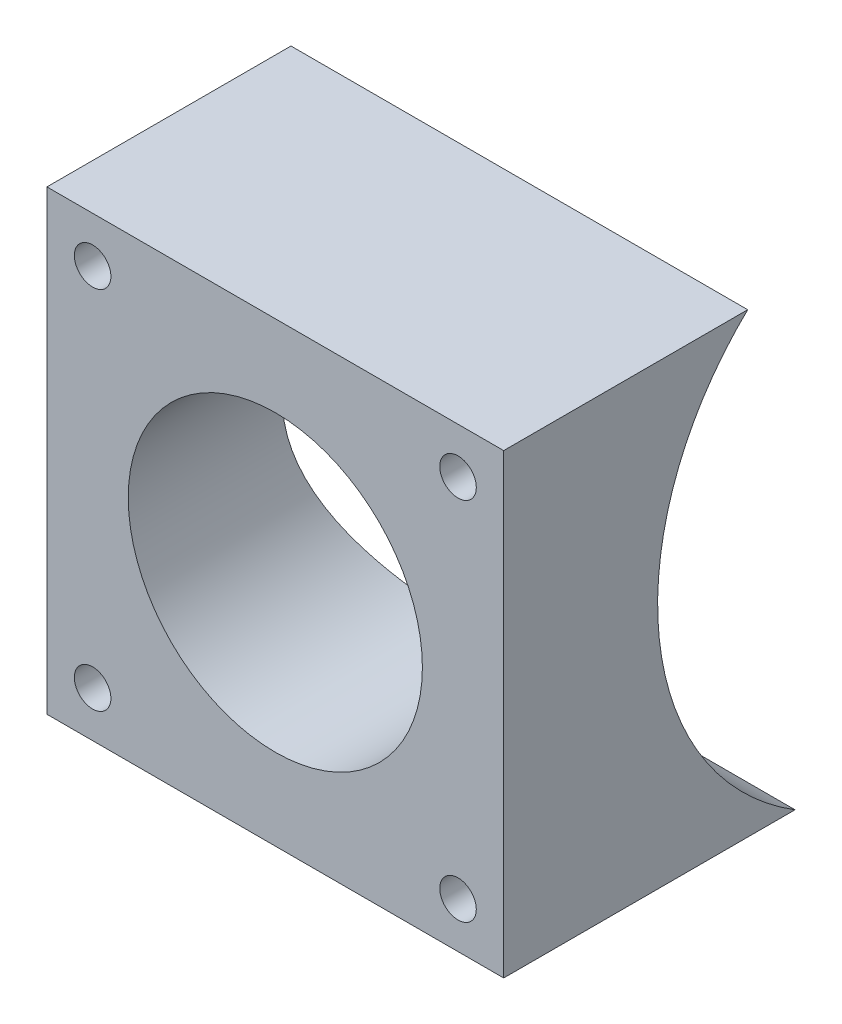
SolidWorks part; units mm, degrees
ref_plane "Front Plane" through (0, 0, 0) normal (0, 0, 1) x (1, 0, 0)
ref_plane "Top Plane" through (0, 0, 0) normal (0, 1, 0) x (1, 0, 0)
ref_plane "Right Plane" through (0, 0, 0) normal (1, 0, 0) x (0, 0, -1)
sketch "Sketch1" plane through (0, 0, 0) normal (0, 0, 1) x (1, 0, 0)
  line L1 (-25, 23) -> (25, 23)
  line L2 (-25, 23) -> (-25, -27)
  line L3 (-25, -27) -> (25, -27)
  line L4 (25, 23) -> (25, -27)
  line L5 (-25, 23) -> (25, -27) construction
  line L6 (-25, -27) -> (25, 23) construction
  circle A0 centre (0, -2) radius 16.1
  circle A1 centre (-20, 18) radius 2
  circle A2 centre (20, 18) radius 2
  circle A3 centre (20, -22) radius 2
  circle A4 centre (-20, -22) radius 2
  point P0 (0, -2)
  dimension "D4" = 32.2
  dimension "D6" = 4
  dimension "D8" = 4
  dimension "D11" = 4
  dimension "D12" = 4
  dimension "D1" = 2
  dimension "D2" = 50
  dimension "D3" = 50
  dimension "D5" = 20
  dimension "D7" = 20
  dimension "D9" = 20
  dimension "D10" = 20
extrude "Boss-Extrude1" add sketch "Sketch1" along normal blind 48.6
sketch "Sketch2" plane through (0, 0, 0) normal (1, 0, 0) x (0, 0, -1)
  circle A0 centre (0, 0) radius 31.75
  dimension "D1" = 63.5
extrude "Cut-Extrude1" cut sketch "Sketch2" against normal through all and the other way through all
